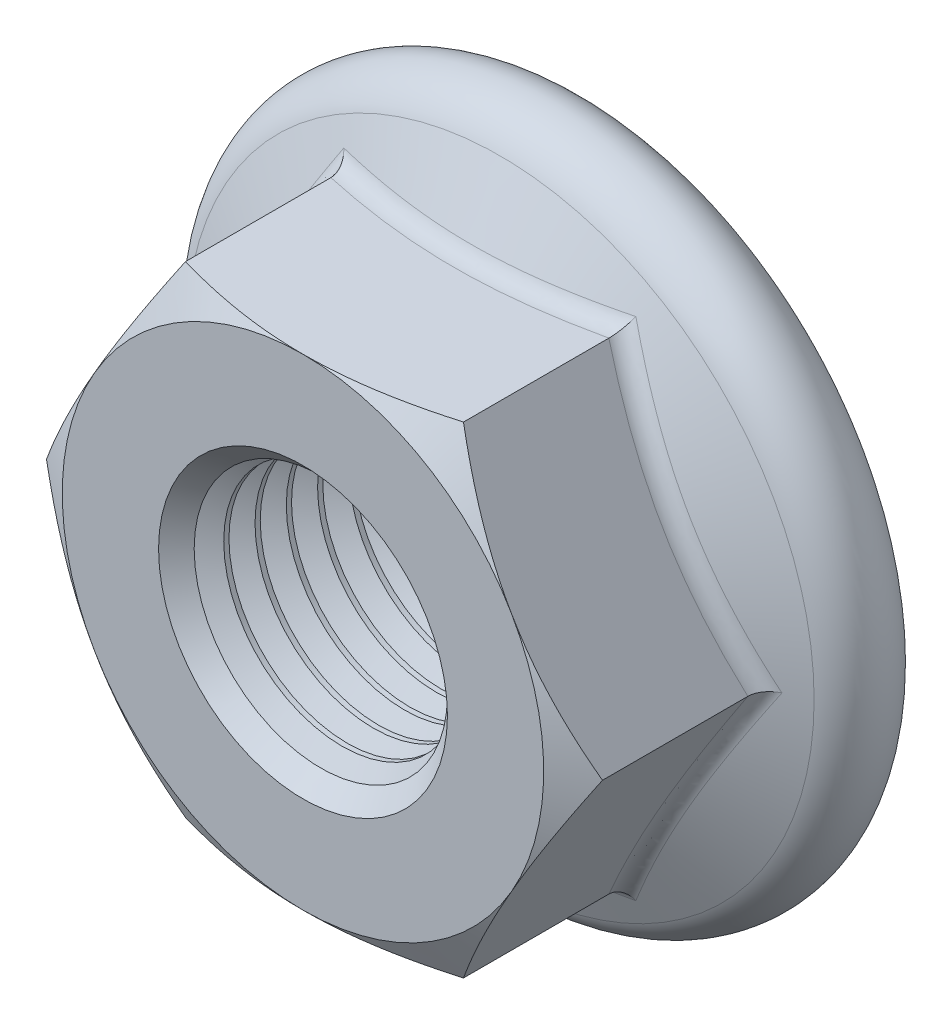
SolidWorks part; units mm, degrees
ref_plane "Front" through (0, 0, 0) normal (0, 0, 1) x (1, 0, 0)
ref_plane "Top" through (0, 0, 0) normal (0, 1, 0) x (1, 0, 0)
ref_plane "Right" through (0, 0, 0) normal (1, 0, 0) x (0, 0, -1)
sketch "Sketch1" plane through (0, 0, 0) normal (0, 0, 1) x (1, 0, 0)
  line L1 (2.8868, -5) -> (5.7735, 0)
  line L2 (5.7735, 0) -> (2.8868, 5)
  line L3 (2.8868, 5) -> (-2.8868, 5)
  line L4 (-2.8868, 5) -> (-5.7735, 0)
  line L5 (-5.7735, 0) -> (-2.8868, -5)
  line L6 (-2.8868, -5) -> (2.8868, -5)
  circle A0 centre (0, 0) radius 5 construction
  circle A1 centre (0, 0) radius 2.4585
  dimension "D1" = 4.917
  dimension "s" = 10
extrude "BaseNut" add sketch "Sketch1" against normal blind 6
cosmetic thread "ThreadCosmetic1" [suppressed] parameters "D2"=6
sketch "Sketch3" plane through (0.6779, 0, -16.6426) normal (0, 1, 0) x (0, 0, -1)
  line L0 (4.0352, 0.6779) -> (-19.0613, 0.6779) construction
  line L2 (-16.6426, 5.6779) -> (-16.196, 6.4514)
  line L4 (-16.196, 6.4514) -> (-16.6426, 6.4514)
  line L5 (-16.6426, 6.4514) -> (-16.6426, 5.6779)
  line L6 (-13.6426, 6.4514) -> (-13.6426, 14.238) construction
  line L8 (-10.6426, 6.4514) -> (-10.6426, 5.6779)
  line L9 (-11.0892, 6.4514) -> (-10.6426, 6.4514)
  line L10 (-10.6426, 5.6779) -> (-11.0892, 6.4514)
  line L11 (-10.6426, 6.4514) -> (-16.6426, 6.4514) construction
  dimension "D1" = 30
  dimension "sq" = 10
revolve "Double-Chamfer" cut sketch "Sketch3" angle 360 about L0
sketch "Sketch4" plane through (4.6827, 0, -16.7173) normal (0, 1, 0) x (0, 0, -1)
  line L0 (-21.7744, 4.6827) -> (9.7398, 4.6827) construction
  line L2 (-14.5188, 30.5008) -> (-14.5188, 8.9315) construction
  line L3 (-12.6236, 11.2053) -> (-14.5188, 7.1412)
  line L4 (-10.7173, 7.1412) -> (-16.7173, 7.1412) construction
  line L5 (-10.7173, 7.1412) -> (-10.7173, 10.7827)
  line L11 (-14.5188, 7.1412) -> (-10.7173, 7.1412)
  arc A0 (-10.7173, 10.7827) -> (-12.6236, 11.2053) centre (-11.7173, 10.7827) ccw
  dimension "m1" = 6
  dimension "dc" = 14.2
  dimension "dw" = 12.2
  dimension "&" = 25
revolve "Flange" add sketch "Sketch4" angle 360 about L0
fillet "FlangeFillet" radius 0.4 6 edges at (-3.6586, -3.6631, -3.4663) (-5.0017, 1.3369, -3.4663) (3.6586, 3.6631, -3.4663) (5.0017, -1.3369, -3.4663)
sketch "Sketch5" plane through (-5.1971, 0, -15.1971) normal (0, 1, 0) x (0, 0, -1)
  line L0 (3.5984, -5.1971) -> (-23.9926, -5.1971) construction
  line L1 (-9.1971, -2.7386) -> (-15.1971, -2.7386) construction
  line L2 (-15.1971, -2.1971) -> (-15.1971, -2.7386)
  line L4 (-15.1971, -2.7386) -> (-14.6556, -2.7386)
  line L6 (-14.6556, -2.7386) -> (-15.1971, -2.1971)
  line L7 (-12.1971, -2.7386) -> (-12.1971, 0.9419) construction
  line L8 (-9.7386, -2.7386) -> (-9.1971, -2.1971)
  line L9 (-9.1971, -2.7386) -> (-9.7386, -2.7386)
  line L10 (-9.1971, -2.1971) -> (-9.1971, -2.7386)
  dimension "da" = 6
  dimension "D2" = 45
revolve "Hole" cut sketch "Sketch5" angle 360 about L0
sketch "Sketch6" plane through (0, 0, 0) normal (0, 1, 0) x (1, 0, 0)
  line L0 (-2.9275, 0.5415) -> (-2.4585, 0.2708)
  line L1 (-2.4585, 0.2708) -> (-1.917, 0.2708)
  line L2 (-1.917, 0.2708) -> (-1.917, 0.8123)
  line L3 (-1.917, 0.8123) -> (-2.4585, 0.8123)
  line L4 (-2.4585, 0.8123) -> (-2.9275, 0.5415)
  line L5 (0, 7.348) -> (0, 34.1252) construction
  dimension "D1" = 0.5415
  dimension "D2" = 4.917
revolve "Cut-Revolve10" cut sketch "Sketch6" angle 360 about L5
pattern_linear "LPattern10" count 9 spacing 0.6498 along (0, 0, -1) of "Cut-Revolve10"
equation "\"m1@Sketch4\" = \"m@BaseNut\""
equation "\"sq@Sketch3\" = \"s@Sketch1\""
equation "\"D2@Sketch6\"=\"D1@Sketch1\""
equation "\"D1@Sketch6\"= (\"D2@ThreadCosmetic1\"  - \"D2@Sketch6\" )  / 2"
equation "\"D3@LPattern10\"=\"D1@Sketch6\" * 1.2 "
equation "\"D1@LPattern10\"=\"m@BaseNut\"  / \"D3@LPattern10\""
